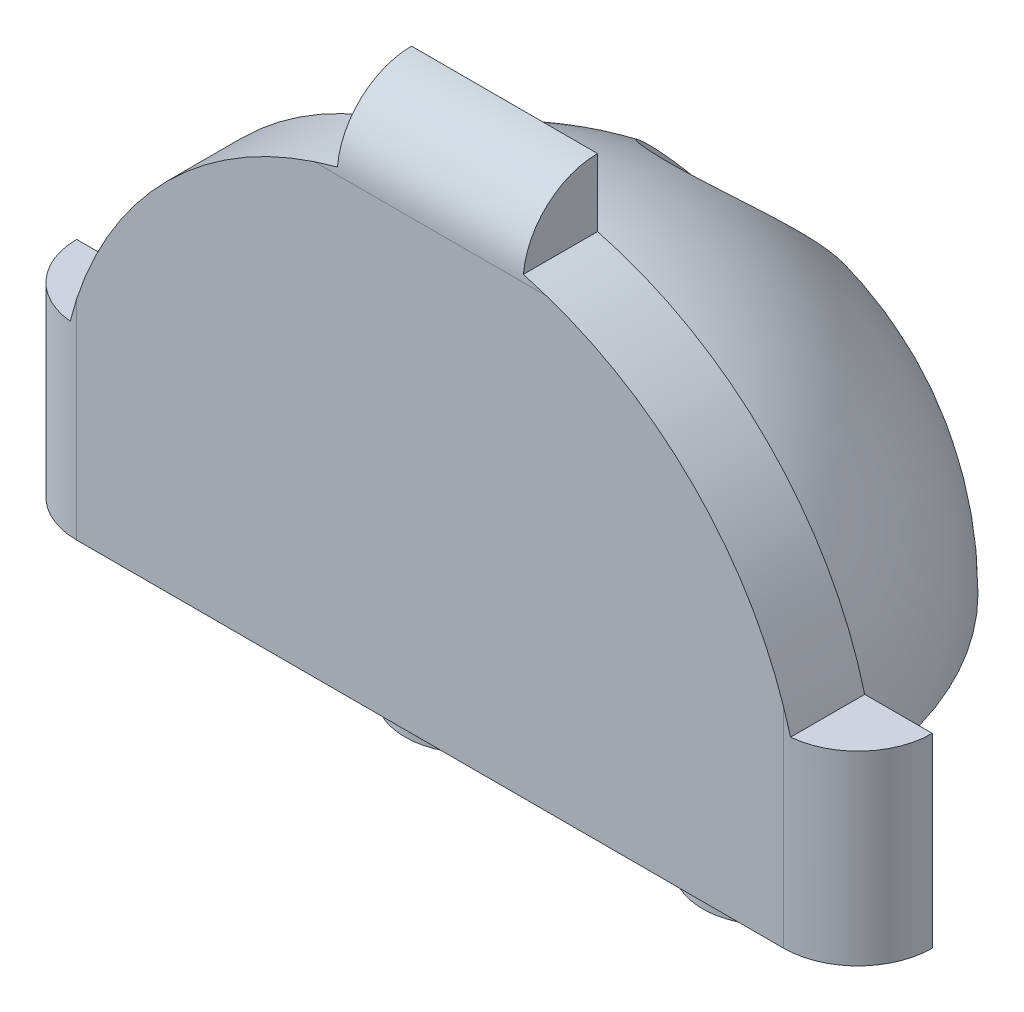
SolidWorks part; units mm, degrees
note: '?' marks a value the reader was unsure of.
ref_plane "前视基准面" through (0, 0, 0) normal (0, 0, 1) x (1, 0, 0)
ref_plane "上视基准面" through (0, 0, 0) normal (0, 1, 0) x (1, 0, 0)
ref_plane "右视基准面" through (0, 0, 0) normal (1, 0, 0) x (0, 0, -1)
other "Configuration Table"
sketch "草图1" plane through (0, 0, 0) normal (0, 0, 1) x (1, 0, 0)
  circle A0 centre (0, 0) radius 10
  dimension "D1" = 20
extrude "凸台-拉伸1" add sketch "草图1" along normal blind 2
sketch "草图2" plane through (0, 0, 0) normal (0, 0, -1) x (-1, 0, 0)
  line L0 (0, 0) -> (0, 10.6664) construction
  line L1 (0, 9) -> (0, 0)
  line L2 (0, 0) -> (9, 0)
  arc A0 (9, 0) -> (0, 9) centre (0, 0) ccw
  dimension "D1" = 9
  dimension "D2" = 9
revolve "旋转1" add sketch "草图2" angle 180 about L0
sketch "草图5" plane through (0, 0, 0) normal (0, -1, 0) x (1, 0, 0)
  circle A0 centre (0, -6.5) radius 2.1
  dimension "D1" = 4.2
  dimension "D2" = 6.5
extrude "切除-拉伸1" cut sketch "草图5" against normal blind 10
sketch "草图6" plane through (0, 0, 0) normal (0, -1, 0) x (1, 0, 0)
  circle A0 centre (-4, -3.1774) radius 1.85
  circle A2 centre (0, -6.5) radius 2.1 construction
  dimension "D1" = 4
  dimension "D2" = 5.2
  dimension "D3" = 3.7
extrude "凸台-拉伸2" add sketch "草图6" along normal blind 6
mirror "镜向1" about plane through (0, 0, 0) normal (1, 0, 0) of "凸台-拉伸2"
sketch "草图7" plane through (0, 0, 0) normal (0, -1, 0) x (1, 0, 0)
  arc A0 (1.9398, -8.7885) -> (-1.9398, -8.7885) centre (0, -6.5) ccw
  circle A1 centre (0, -6.5) radius 2.1 construction
  circle A2 centre (0, -6.5) radius 2.1
  arc A3 (-9, 0) -> (9, 0) centre (0, 0) ccw construction
  arc A4 (-1.9398, -8.7885) -> (1.9398, -8.7885) centre (0, 0) ccw
  dimension "D1" = 6
extrude "凸台-拉伸3" add sketch "草图7" along normal blind 1.38
ref_axis "基准轴1" through (4, -6, -3.1774) along (0, 1, 0)?
ref_axis "基准轴2" through (-4, -6, -3.1774) along (0, 1, 0)?
ref_plane "基准面1" through (0, 0, -3.1774) normal (0, 0, 1) x (1, 0, 0)
sketch "草图8" plane through (0, 0, -3.1774) normal (0, 0, 1) x (1, 0, 0)
  line L0 (4, -5.3) -> (4, -3.4952) construction
  line L1 (2.15, -6) -> (5.85, -6) construction
  line L2 (4, -3.6758) -> (2.15, -3.6758)
  line L3 (2.15, 0) -> (2.15, -6) construction
  line L4 (2.15, -3.6758) -> (2, -4.0879)
  line L5 (2, -4.0879) -> (2, -4.8879)
  line L6 (2, -4.8879) -> (2.15, -5.3)
  line L7 (2.15, -5.3) -> (4, -5.3)
  line L8 (4, -5.3) -> (4, -3.6758)
  line L9 (4, -6) -> (4, 0) construction
  dimension "D1" = 4
  dimension "D2" = 160
  dimension "D3" = 160
  dimension "D4" = 0.8
  dimension "D5" = 0.7
revolve "旋转2" add sketch "草图8" angle 360 about L0
mirror "镜向2" about plane through (0, 0, 0) normal (1, 0, 0) of "旋转2"
sketch "草图10" plane through (0, 0, 2) normal (0, 0, 1) x (1, 0, 0)
  line L5 (-2.5, -11.5) -> (2.5, -11.5)
  line L6 (-2.5, -11.5) -> (-2.5, 11.5)
  line L7 (-2.5, 11.5) -> (2.5, 11.5)
  line L8 (2.5, -11.5) -> (2.5, 11.5)
  line L9 (-2.5, -11.5) -> (2.5, 11.5) construction
  line L10 (-2.5, 11.5) -> (2.5, -11.5) construction
  point P0 (0, 0)
  dimension "D1" = 5
  dimension "D2" = 23
extrude "凸台-拉伸4" add sketch "草图10" against normal blind 2
pattern_circular "阵列(圆周)3" count 4 over 360 about axis through (0, 0, 0) along (0, 0, 1) of "凸台-拉伸4"
fillet "圆角3" radius 2 20 edges at (-11.5, -2.5, 1) (-2.5, 10.5912, 2) (2.5, 10.5912, 2) (0, 11.5, 2) (2.5, 11.5, 1) (2.5, -11.5, 1) (-2.5, -11.5, 1) (-2.5, 11.5, 1) (2.5, -10.5912, 2) (-2.5, -10.5912, 2) (0, -11.5, 2) (11.5, -2.5, 1) (10.5912, 2.5, 2) (10.5912, -2.5, 2) (11.5, 0, 2) (-10.5912, -2.5, 2) (-10.5912, 2.5, 2) (-11.5, 0, 2) (-11.5, 2.5, 1) (11.5, 2.5, 1)
sketch "草图11" plane through (0, 0, 0) normal (0, 0, -1) x (-1, 0, 0)
  line L1 (-9.6825, -2.5) -> (9.6825, -2.5)
  line L2 (-9.6825, -2.5) -> (-9.6825, -14.5451)
  line L3 (-9.6825, -14.5451) -> (9.6825, -14.5451)
  line L4 (9.6825, -2.5) -> (9.6825, -14.5451)
  line L6 (11.5, -2.5) -> (9.6825, -2.5) construction
  dimension "D1" = 12.0451
extrude "切除-拉伸2" cut sketch "草图11" against normal blind 10
